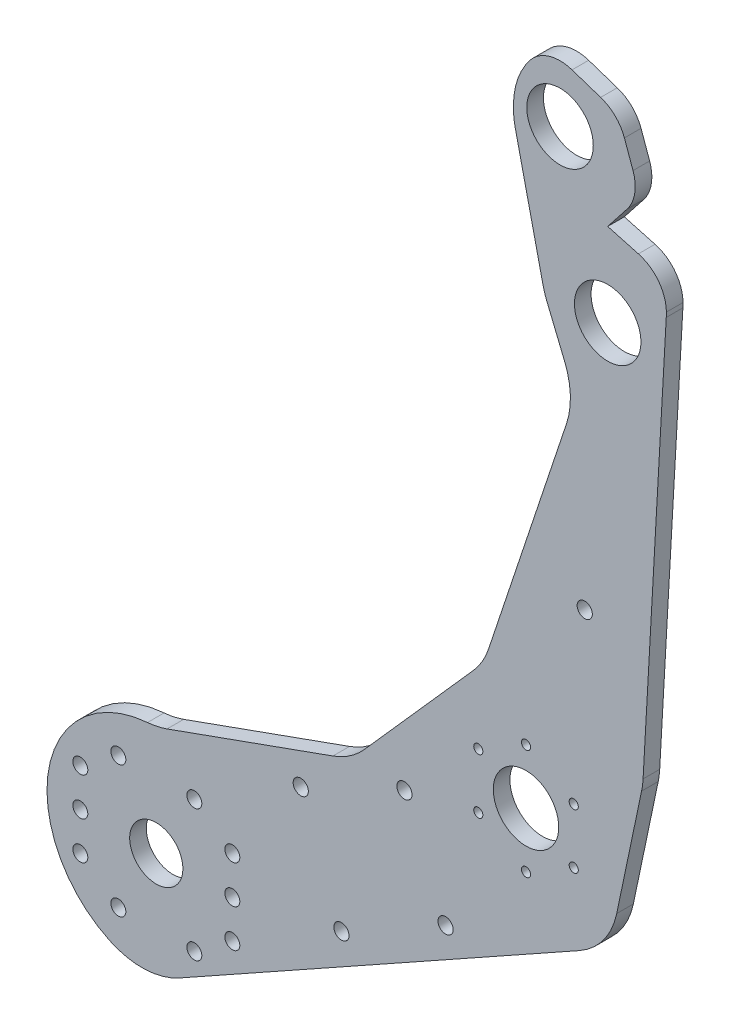
SolidWorks part; units mm, degrees
ref_plane "Front Plane" through (0, 0, 0) normal (0, 0, 1) x (1, 0, 0)
ref_plane "Top Plane" through (0, 0, 0) normal (0, 1, 0) x (1, 0, 0)
ref_plane "Right Plane" through (0, 0, 0) normal (1, 0, 0) x (0, 0, -1)
sketch "Sketch1" plane through (0, 0, 0) normal (0, 0, 1) x (1, 0, 0)
  line L0 (199.796, 71.0781) -> (188.9649, 57.2856)
  line L1 (38.107, -163.0696) -> (103.2618, -139.7016)
  line L2 (103.2618, -139.7016) -> (147.5504, -89.7457)
  line L3 (147.5504, -89.7457) -> (171.8362, -16.8147)
  line L4 (171.8362, -16.8147) -> (178.1894, 2.2642)
  line L5 (178.1894, 2.2642) -> (167.83, 27.4472)
  line L6 (157.4706, 73.0101) -> (157.4706, 93.39)
  line L7 (157.4706, 93.39) -> (170.6001, 98.791)
  line L8 (170.6001, 98.791) -> (192.4684, 91.509)
  line L9 (192.4684, 91.509) -> (199.796, 71.0781)
  line L10 (208.8308, 45.8872) -> (200.6841, -98.6168)
  line L11 (200.6841, -98.6168) -> (189.6112, -151.3856)
  line L12 (189.6112, -151.3856) -> (38.107, -236.12)
  line L13 (188.9649, 57.2856) -> (206.4568, 52.5065)
  line L14 (206.4568, 52.5065) -> (208.8308, 45.8872)
  line L15 (157.4706, 73.0101) -> (167.83, 27.4472)
  line L16 (200.3291, 52.5254) -> (188.9649, 57.2856) construction
  arc A9 (38.107, -163.0696) -> (38.107, -236.12) centre (38.107, -199.5948) ccw
  circle A10 centre (38.107, -199.5948) radius 8.89
  circle A11 centre (161.6717, -124.7706) radius 10.9347
  circle A12 centre (188.9649, 29.3961) radius 11.1125
  circle A13 centre (173.036, 78.2376) radius 11.1125
  circle A18 centre (161.6717, -106.3556) radius 1.524
  circle A19 centre (12.7212, -186.891) radius 2.5
  circle A20 centre (177.6196, -115.5631) radius 1.524
  circle A21 centre (177.6196, -133.9781) radius 1.524
  circle A22 centre (161.6717, -143.1856) radius 1.524
  circle A23 centre (145.7239, -133.9781) radius 1.524
  circle A24 centre (145.7239, -115.5631) radius 1.524
  circle A25 centre (181.2925, -57.5107) radius 2.54 construction
  circle A26 centre (99.969, -191.2309) radius 2.54 construction
  circle A27 centre (12.7212, -199.591) radius 2.5
  circle A28 centre (12.7212, -212.291) radius 2.5
  circle A29 centre (25.4212, -221.5881) radius 2.5
  circle A30 centre (25.4212, -177.594) radius 2.5
  circle A31 centre (50.8212, -177.594) radius 2.5
  circle A32 centre (63.5212, -186.891) radius 2.5
  circle A33 centre (63.5212, -199.591) radius 2.5
  circle A34 centre (63.5212, -212.291) radius 2.5
  circle A35 centre (50.8212, -221.5881) radius 2.5
  circle A36 centre (134.7824, -172.0835) radius 2.54 construction
  circle A37 centre (121.0311, -139.8965) radius 2.54 construction
  circle A38 centre (86.3918, -156.2435) radius 2.54 construction
  circle A39 centre (181.2925, -57.5107) radius 2.54
  circle A40 centre (99.969, -191.2309) radius 2.54
  circle A41 centre (134.7824, -172.0835) radius 2.54
  circle A42 centre (121.0311, -139.8965) radius 2.54
  circle A43 centre (86.3918, -156.2435) radius 2.54
  point P33 (38.107, -199.5948)
  dimension "D1" = 22.225
  dimension "D2" = 22.225
  dimension "D3" = 17.78
  dimension "D5" = 73.0504
  dimension "D6" = 21.8694
  dimension "D7" = 3.048
  dimension "D8" = 18.415
extrude "Boss-Extrude1" add sketch "Sketch1" along normal blind 5.5562
fillet "Fillet1" radius 25.4 11 edges at (157.4706, 93.39, 2.7781) (157.4706, 73.0101, 2.7781) (167.83, 27.4472, 2.7781) (178.1894, 2.2642, 2.7781) (147.5504, -89.7457, 2.7781) (103.2618, -139.7016, 2.7781) (38.107, -163.0696, 2.7781) (38.107, -236.12, 2.7781) (189.6112, -151.3856, 2.7781) (200.6841, -98.6168, 2.7781) (208.8308, 45.8872, 2.7781)
fillet "Fillet3" radius 12.7 2 edges at (192.4684, 91.509, 2.7781) (170.6001, 98.791, 2.7781)
fillet "Fillet4" radius 12.7 2 edges at (206.4568, 52.5065, 2.7781) (199.796, 71.0781, 2.7781)
